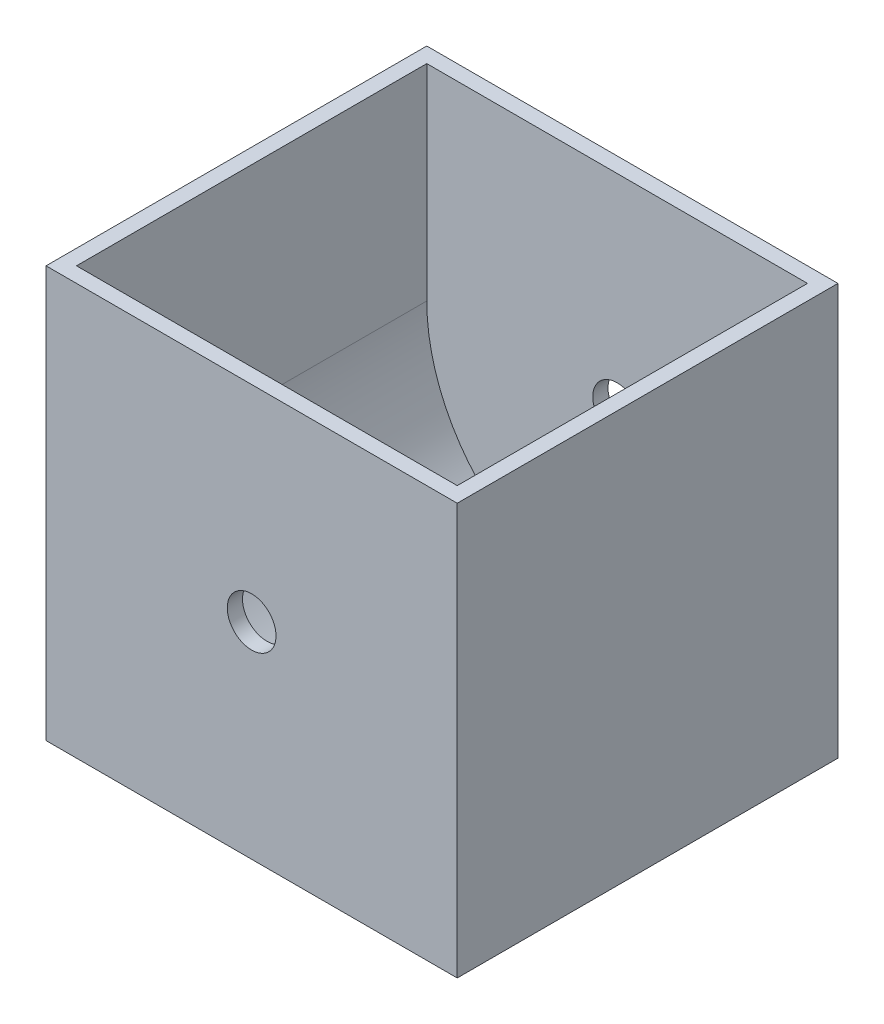
SolidWorks part; units mm, degrees
ref_plane "Front Plane" through (0, 0, 0) normal (0, 0, 1) x (1, 0, 0)
ref_plane "Top Plane" through (0, 0, 0) normal (0, 1, 0) x (1, 0, 0)
ref_plane "Right Plane" through (0, 0, 0) normal (1, 0, 0) x (0, 0, -1)
sketch "Sketch2" plane through (0, 0, 0) normal (0, 0, 1) x (1, 0, 0)
  line L0 (5, 67.5) -> (130, 67.5)
  line L1 (0, 0) -> (135, 0)
  line L2 (0, 0) -> (0, 135)
  line L3 (0, 135) -> (135, 135)
  line L4 (135, 0) -> (135, 135)
  circle A0 centre (67.5, 67.5) radius 62.5
  circle A1 centre (67.5, 67.5) radius 8
  dimension "D3" = 125
  dimension "D4" = 16
  dimension "D1" = 135
  dimension "D2" = 135
extrude "Boss-Extrude3" add sketch "Sketch2" against normal blind 5 contours A1 L0 A0 | A1 L0 A0 | L1 L4 L3 L2 A0 region at (67.5, 94.4111, 0) region at (67.5, 40.5889, 0) region at (1.9092, 67.5, 0)
extrude "Boss-Extrude4" add sketch "Sketch2<3>" along normal blind 120 contours L2 L3 L4 L1
sketch "Sketch2<3>" plane through (0, 0, 0) normal (0, 0, 1) x (1, 0, 0) same geometry as "Sketch2"
sketch "Sketch3" plane through (0, 135, 0) normal (0, 1, 0) x (1, 0, 0)
  line L3 (135, 5) -> (135, -120) construction
  line L4 (130, 0) -> (5, 0)
  line L5 (130, 0) -> (130, -115)
  line L6 (130, -115) -> (5, -115)
  line L7 (5, 0) -> (5, -115)
  point P6 (67.5, -57.5)
  dimension "D2" = 5
extrude "Cut-Extrude1" cut sketch "Sketch3" against normal blind 67.5 contours L7 L6 L5 L4
extrude "Cut-Extrude2" cut sketch "Sketch2<5>" along normal blind 115 contours L0 A0 | A1 region at (67.5, 40.5889, 0)
sketch "Sketch2<5>" plane through (0, 0, 0) normal (0, 0, 1) x (1, 0, 0) same geometry as "Sketch2"
extrude "Cut-Extrude3" cut sketch "Sketch2<6>" along normal blind 120 contours A1
sketch "Sketch2<6>" plane through (0, 0, 0) normal (0, 0, 1) x (1, 0, 0) same geometry as "Sketch2"
